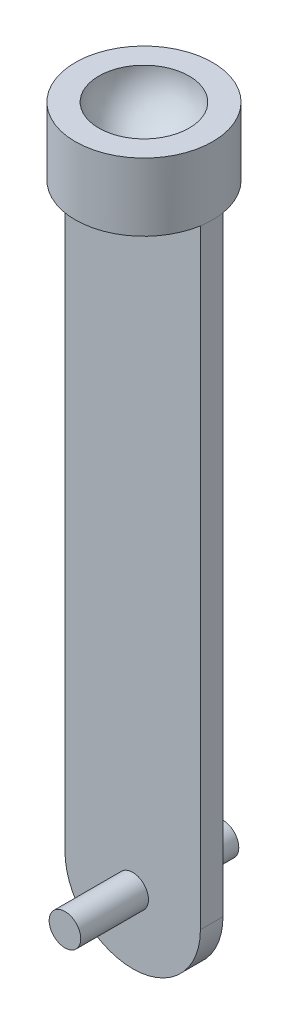
SolidWorks part; units mm, degrees
ref_plane "Front Plane" through (0, 0, 0) normal (0, 0, 1) x (1, 0, 0)
ref_plane "Top Plane" through (0, 0, 0) normal (0, 1, 0) x (1, 0, 0)
ref_plane "Right Plane" through (0, 0, 0) normal (1, 0, 0) x (0, 0, -1)
sketch "Sketch1" plane through (0, 0, 0) normal (0, 0, 1) x (1, 0, 0)
  line L2 (-15, -75) -> (-15, 75)
  line L3 (-15, 75) -> (15, 75)
  line L4 (15, -75) -> (15, 75)
  line L5 (-15, -75) -> (15, 75) construction
  line L6 (-15, 75) -> (15, -75) construction
  arc A0 (-15, -75) -> (15, -75) centre (0, -75) ccw
  point P0 (0, 0)
  dimension "D1" = 150
  dimension "D2" = 30
extrude "Boss-Extrude1" add sketch "Sketch1" along normal mid plane 5
sketch "Sketch4" plane through (0, 75, 0) normal (0, 1, 0) x (1, 0, 0)
  circle A0 centre (0, 0) radius 15.2069
extrude "Boss-Extrude2" add sketch "Sketch4" against normal blind 15
sketch "Sketch6" plane through (0, 0, 0) normal (0, 0, 1) x (1, 0, 0)
  line L0 (15.2069, 75) -> (-15.2069, 75) construction
  line L1 (0, 75) -> (0, 65) construction
  line L2 (0, 75) -> (10, 75)
  line L4 (0, 75) -> (0, 65)
  arc A0 (10, 75) -> (0, 65) centre (0, 75) cw
  dimension "D1" = 20
revolve "Cut-Revolve3" cut sketch "Sketch6" angle 360 about L1
sketch "Sketch7" plane through (0, 0, 2.5) normal (0, 0, 1) x (1, 0, 0)
  circle A0 centre (0, -75) radius 3.5
  dimension "D1" = 7
extrude "Boss-Extrude3" add sketch "Sketch7" along normal blind 15
mirror "Mirror1" about plane through (0, 0, 0) normal (0, 0, 1) of "Boss-Extrude3"
